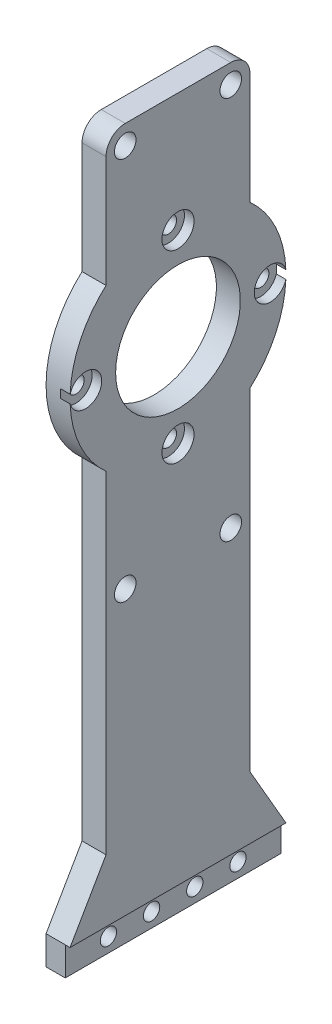
SolidWorks part; units mm, degrees
material "Сплав 2024"
ref_plane "Спереди" through (0, 0, 0) normal (0, 0, 1) x (1, 0, 0)
ref_plane "Сверху" through (0, 0, 0) normal (0, 1, 0) x (1, 0, 0)
ref_plane "Справа" through (0, 0, 0) normal (1, 0, 0) x (0, 0, -1)
sketch "Эскиз1" plane through (0, 0, 0) normal (0, 1, 0) x (1, 0, 0)
  line L1 (0, 0) -> (5, 0)
  line L2 (0, 0) -> (0, -30)
  line L3 (0, -30) -> (5, -30)
  line L4 (5, 0) -> (5, -30)
  dimension "D1" = 5
  dimension "D2" = 30
extrude "Бобышка-Вытянуть1" add sketch "Эскиз1" along normal blind 177
sketch "Эскиз2" plane through (0, 0, 0) normal (-1, 0, 0) x (0, 0, 1)
  line L0 (30, 105) -> (0, 105) construction
  line L3 (15, 177) -> (15, 0) construction
  line L4 (0, 177) -> (30, 177) construction
  line L5 (0, 0) -> (30, 0) construction
  line L6 (30, 0) -> (0, 0) construction
  circle A0 centre (15, 105) radius 22.5
  dimension "D1" = 45
  dimension "D2" = 105
extrude "Бобышка-Вытянуть2" add sketch "Эскиз2" against normal up to surface (5 mm away) up to face at (5, 88.5, 15)
sketch "Эскиз3" plane through (0, 0, 0) normal (-1, 0, 0) x (0, 0, 1)
  circle A0 centre (15, 105) radius 13
  dimension "D1" = 26
extrude "Вырез-Вытянуть1" cut sketch "Эскиз3" against normal through all
sketch "Эскиз4" plane through (5, 0, 0) normal (-1, 0, 0) x (0, 0, 1)
  line L0 (15, 127.5) -> (15, 82.5) construction
  line L1 (15, 177) -> (15, 0) construction
  line L2 (37.5, 105) -> (-7.5, 105) construction
  circle A0 centre (15, 105) radius 19.25 construction
  circle A1 centre (15, 105) radius 22.5 construction
  dimension "D1" = 38.5
hole_wizard "Цековка для  винта с полукруглой головкой M31" positions "Эскиз6" profile "Эскиз5" counterbore size "M3" standard "Ansi Metric" end condition through all
sketch "Эскиз6" plane through (5, -25.0247, 7.2629) normal (-1, 0, 0) x (0, 0, 1)
  line L0 (7.7371, 152.5247) -> (7.7371, 107.5247) construction
  line L1 (30.2371, 130.0247) -> (-14.7629, 130.0247) construction
  circle A0 centre (7.7371, 130.0247) radius 19.25 construction
  point P0 (7.7371, 149.2747)
  point P6 (-11.5129, 130.0247)
  point P10 (7.7371, 110.7747)
  point P12 (26.9871, 130.0247)
sketch "Эскиз5" plane through (5, 124.25, 15) normal (0, 1, 0) x (0, 0, -1)
  line L0 (0, 0) -> (0, 5)
  line L1 (0, 5) -> (1.7, 5)
  line L3 (1.7, 5) -> (1.7, 2)
  line L4 (1.7, 2) -> (3.35, 2)
  line L5 (3.35, 2) -> (3.35, 0)
  line L7 (3.35, 0) -> (0, 0)
  line L11 (0, -6.35) -> (0, 107.95) construction
  dimension "Диаметр сквозного отверстия" = 3.4
  dimension "Глубина сквозного отверстия" = 5
  dimension "Диаметр цековки" = 6.7
  dimension "Глубина цековки" = 2
sketch "Эскиз8" plane through (5, 0, 0) normal (1, 0, 0) x (0, 0, -1)
  line L0 (-15, 177) -> (-15, 0) construction
  line L1 (-30, 177) -> (0, 177) construction
  line L2 (-30, 0) -> (0, 0) construction
  line L3 (19.447, 105) -> (-49.447, 105) construction
  line L4 (0, 177) -> (0, 121.7705) construction
  line L5 (-26, 145) -> (-4, 145) construction
  line L6 (-26, 145) -> (-26, 65) construction
  line L7 (-26, 65) -> (-4, 65) construction
  line L8 (-4, 145) -> (-4, 65) construction
  line L9 (-26, 145) -> (-4, 65) construction
  line L10 (-26, 65) -> (-4, 145) construction
  line L11 (-30, 105) -> (0, 105) construction
  point P8 (-15, 105)
  point P9 (-15, 105)
  dimension "D1" = 4
  dimension "D2" = 80
hole_wizard "Отверстие с зазором M41" positions "Эскиз10" profile "Эскиз9" hole size "M4" standard "Ansi Metric" end condition through all
sketch "Эскиз10" plane through (5, 0, 0) normal (1, 0, 0) x (0, 0, -1)
  point P0 (-26, 145)
  point P3 (-4, 145)
  point P6 (-4, 65)
  point P9 (-26, 65)
sketch "Эскиз9" plane through (5, 145, 26) normal (0, 1, 0) x (0, 0, -1)
  line L0 (0, 0) -> (0, 5)
  line L1 (0, 5) -> (2.25, 5)
  line L2 (2.25, 5) -> (2.25, 0)
  line L5 (2.25, 0) -> (0, 0)
  line L11 (0, -6.35) -> (0, 107.95) construction
  dimension "Диаметр сквозного отверстия" = 4.5
  dimension "Глубина сквозного отверстия" = 5
sketch "Эскиз11" plane through (5, 0, 0) normal (1, 0, 0) x (0, 0, -1)
  line L0 (-30, 0) -> (0, 0) construction
  line L1 (-15, 177) -> (-15, 0) construction
  line L2 (-30, 177) -> (0, 177) construction
  line L3 (0, 88.2295) -> (0, 0) construction
  line L4 (-30, 88.2295) -> (-30, 0) construction
  line L5 (-37.5, 3) -> (7.5, 3) construction
  line L20 (-1.5, 0) -> (-1.5, 6) construction
  line L21 (-10.5, 0) -> (-10.5, 6) construction
  line L22 (-19.5, 0) -> (-19.5, 6) construction
  line L23 (-28.5, 0) -> (-28.5, 6) construction
  line L25 (-37.5, 0) -> (7.5, 6) construction
  line L26 (-37.5, 6) -> (7.5, 0) construction
  line L27 (-37.5, 6) -> (7.5, 6) construction
  line L28 (0, 18.9904) -> (7.5, 6)
  line L29 (-30, 18.9904) -> (0, 18.9904)
  line L30 (7.5, 6) -> (7.5, 0)
  line L31 (-37.5, 0) -> (7.5, 0)
  line L32 (-37.5, 6) -> (-37.5, 0)
  line L33 (-37.5, 6) -> (-30, 18.9904)
  point P2 (-15, 3)
  dimension "D1" = 45
  dimension "D2" = 6
  dimension "D3" = 9
  dimension "D4" = 9
  dimension "D5" = 9
  dimension "D6" = 9
  dimension "D7" = 120
extrude "Бобышка-Вытянуть3" add sketch "Эскиз11" against normal up to surface (5 mm away) up to face at (0, 145, 23.75)
hole_wizard "Отверстие с зазором M31" positions "Эскиз13" profile "Эскиз12" hole size "M3" standard "Ansi Metric" end condition through all
sketch "Эскиз13" plane through (5, 0, 0) normal (1, 0, 0) x (0, 0, -1)
  line L4 (-28.5, 0) -> (-28.5, 6) construction
  line L5 (-19.5, 0) -> (-19.5, 6) construction
  line L6 (-10.5, 0) -> (-10.5, 6) construction
  line L7 (-1.5, 0) -> (-1.5, 6) construction
  point P16 (-28.5, 3)
  point P20 (-19.5, 3)
  point P24 (-10.5, 3)
  point P28 (-1.5, 3)
sketch "Эскиз12" plane through (5, 3, 28.5) normal (0, 1, 0) x (0, 0, -1)
  line L0 (0, 0) -> (0, 5)
  line L1 (0, 5) -> (1.7, 5)
  line L2 (1.7, 5) -> (1.7, 0)
  line L5 (1.7, 0) -> (0, 0)
  line L11 (0, -6.35) -> (0, 107.95) construction
  dimension "Диаметр сквозного отверстия" = 3.4
  dimension "Глубина сквозного отверстия" = 5
sketch "Эскиз14" plane through (5, 0, 0) normal (1, 0, 0) x (0, 0, -1)
  line L5 (-37.5, 0) -> (7.5, 0)
  line L6 (-37.5, 0) -> (-37.5, 6)
  line L7 (-37.5, 6) -> (7.5, 6)
  line L8 (7.5, 0) -> (7.5, 6)
extrude "Вырез-Вытянуть2" cut sketch "Эскиз14" against normal blind 1
sketch "Эскиз15" plane through (5, 0, 0) normal (1, 0, 0) x (0, 0, -1)
  line L0 (0, 177) -> (0, 121.7705) construction
  line L1 (-30, 177) -> (0, 177)
  line L2 (-30, 177) -> (-30, 149.0245)
  line L3 (-30, 149.0245) -> (0, 149.0245)
  line L4 (0, 177) -> (0, 149.0245)
  circle A0 centre (-26, 145) radius 2.25 construction
  dimension "D1" = 4.0245
extrude "Вырез-Вытянуть3" cut sketch "Эскиз15" against normal up to surface (5 mm away) up to face at (0, 3, 26.8)
fillet "Скругление1" radius 4 2 edges at (2.5, 149.0245, 30) (2.5, 149.0245, 0)
equation "\"D4@Эскиз11\"=\"D3@Эскиз11\""
equation "\"D5@Эскиз11\"=\"D3@Эскиз11\""
equation "\"D6@Эскиз11\"=\"D4@Эскиз11\""
equation "\"D3@Эскиз11\" = \"D1@Эскиз11\" / 5"
